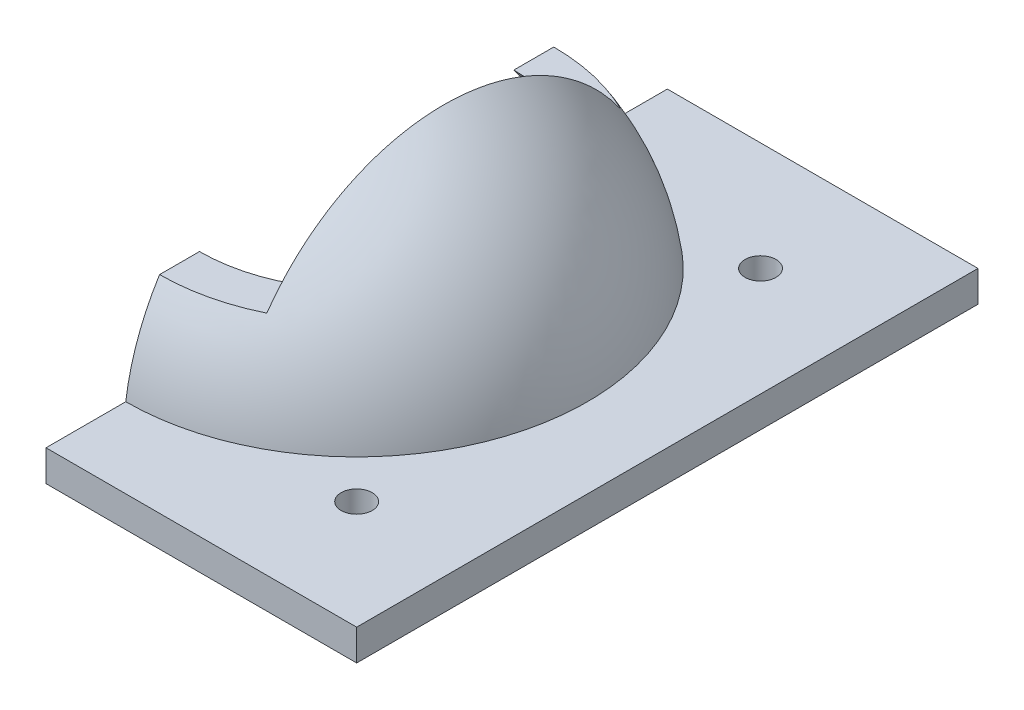
SolidWorks part; units mm, degrees
ref_plane "Front Plane" through (0, 0, 0) normal (0, 0, 1) x (1, 0, 0)
ref_plane "Top Plane" through (0, 0, 0) normal (0, 1, 0) x (1, 0, 0)
ref_plane "Right Plane" through (0, 0, 0) normal (1, 0, 0) x (0, 0, -1)
sketch "Sketch1" plane through (0, 0, 0) normal (0, 0, 1) x (1, 0, 0)
  line L0 (16.383, 0) -> (19.05, 0) construction
  line L1 (19.05, 0) -> (16.383, 0) construction
  line L2 (19.05, 0) -> (16.383, 0)
  line L3 (0, 19.05) -> (0, 16.383)
  arc A0 (19.05, 0) -> (0, 19.05) centre (0, 0) ccw
  arc A2 (16.383, 0) -> (0, 16.383) centre (0, 0) ccw
  circle A3 centre (0, 0) radius 19.05 construction
  circle A4 centre (0, 0) radius 16.383 construction
  dimension "D1" = 38.1
  dimension "D2" = 2.667
revolve "Revolve1" add sketch "Sketch1" angle 360 about L3
sketch "Sketch2" plane through (0, 0, 0) normal (0, 0, 1) x (1, 0, 0)
  line L0 (0, 10.16) -> (0, 0) construction
  line L1 (-7.112, 22.7688) -> (7.112, 22.7688)
  line L2 (-7.112, 22.7688) -> (-7.112, 10.16)
  line L3 (-7.112, 10.16) -> (7.112, 10.16)
  line L4 (7.112, 22.7688) -> (7.112, 10.16)
  dimension "D1" = 10.16
  dimension "D2" = 14.224
extrude "Cut-Extrude1" cut sketch "Sketch2" against normal mid plane 127
sketch "Sketch3" plane through (0, 0, 0) normal (0, -1, 0) x (1, 0, 0)
  line L1 (25.4, -25.4) -> (-25.4, -25.4)
  line L2 (25.4, -25.4) -> (25.4, 25.4)
  line L3 (25.4, 25.4) -> (-25.4, 25.4)
  line L4 (-25.4, -25.4) -> (-25.4, 25.4)
  line L5 (25.4, -25.4) -> (-25.4, 25.4) construction
  line L6 (25.4, 25.4) -> (-25.4, -25.4) construction
  circle A0 centre (0, 0) radius 16.51
  point P0 (0, 0)
  dimension "D2" = 33.02
  dimension "D1" = 50.8
sketch "Sketch4" plane through (0, 0, 0) normal (0, -1, 0) x (1, 0, 0)
  line L0 (25.4, -25.4) -> (-25.4, 25.4) construction
  circle A0 centre (0.1236, -0.1236) radius 16.51
  dimension "D1" = 33.02
extrude "Boss-Extrude1" add sketch "Sketch3" against normal blind 2.54
sketch "Sketch5" plane through (0, 2.54, 0) normal (0, 1, 0) x (1, 0, 0)
  line L0 (-16.51, 25.4) -> (-16.51, 16.51) construction
  line L1 (-25.4, 25.4) -> (25.4, 25.4) construction
  line L2 (-16.51, 16.51) -> (-25.4, 16.51) construction
  line L3 (-25.4, -25.4) -> (-25.4, 25.4) construction
  circle A0 centre (-16.51, 16.51) radius 1.27
  dimension "D2" = 2.54
  dimension "D1" = 8.89
extrude "Cut-Extrude3" cut sketch "Sketch5" against normal through all contours A0
pattern_linear "LPattern1" count 2 spacing 33.02 along (1, 0, 0) count 2 spacing 33.02 along (0, 0, 1) of "Cut-Extrude3"
sketch "Sketch7" plane through (-25.4, 0, 0) normal (-1, 0, 0) x (0, 0, 1)
  line L1 (27.5805, -2.6409) -> (-28.3451, -2.6409)
  line L2 (27.5805, -2.6409) -> (27.5805, 22.1646)
  line L3 (27.5805, 22.1646) -> (-28.3451, 22.1646)
  line L4 (-28.3451, -2.6409) -> (-28.3451, 22.1646)
extrude "Cut-Extrude4" cut sketch "Sketch7" against normal blind 25.4
